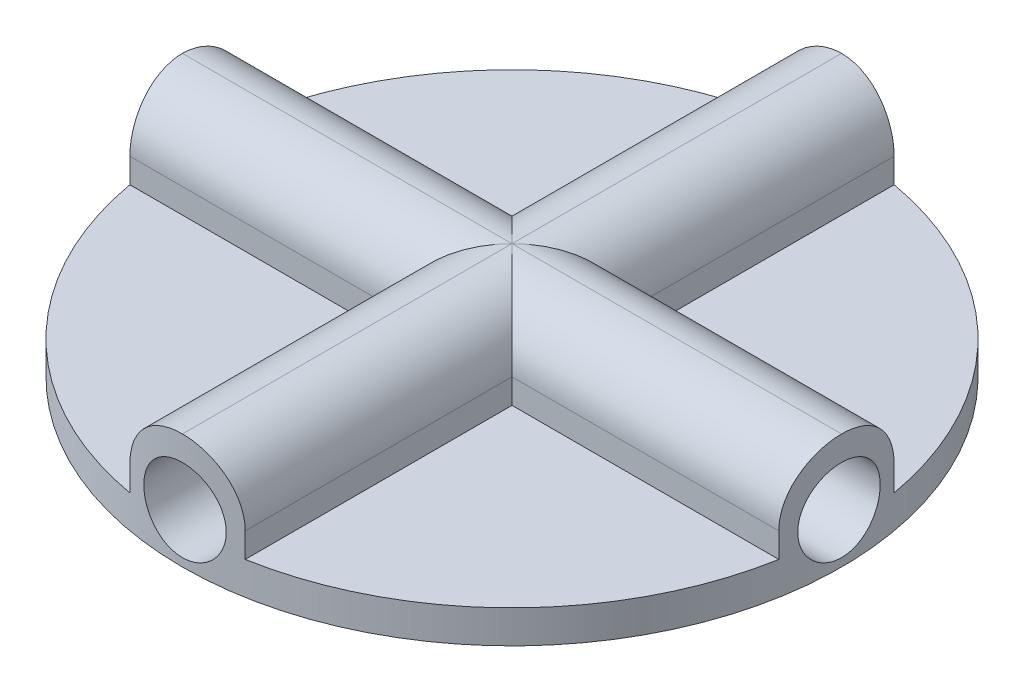
SolidWorks part; units mm, degrees
ref_plane "Front Plane" through (0, 0, 0) normal (0, 0, 1) x (1, 0, 0)
ref_plane "Top Plane" through (0, 0, 0) normal (0, 1, 0) x (1, 0, 0)
ref_plane "Right Plane" through (0, 0, 0) normal (1, 0, 0) x (0, 0, -1)
sketch "Sketch1" plane through (0, 0, 0) normal (0, 1, 0) x (1, 0, 0)
  circle A0 centre (0, 0) radius 20
  circle A1 centre (0, 0) radius 3
  dimension "D1" = 40
  dimension "D2" = 6
extrude "Boss-Extrude1" add sketch "Sketch1" along normal blind 7 contours A0
sketch "Sketch8" plane through (0, 0, 0) normal (0, 0, 1) x (1, 0, 0)
  line L0 (-20, 0) -> (20, 0) construction
  circle A0 centre (0, 3) radius 2.5
  point P2 (0, 3.3742)
  dimension "D1" = 5
  dimension "3" = 3
extrude "Cut-Extrude4" cut sketch "Sketch8" against normal up to surface (19.8431 mm away) up to face at (0, 7, 20)
pattern_circular "CirPattern9" count 4 over 360 about axis through (0, 7, 0) along (0, -1, 0) of "Cut-Extrude4" reverse direction yes
sketch "Sketch9" plane through (0, 7, 0) normal (0, 1, 0) x (1, 0, 0)
  line L0 (-3.5, -3.5) -> (-3.5, -19.6914)
  line L1 (-3.5, -19.6914) -> (-22.3802, -19.6914)
  line L2 (-22.3802, -19.6914) -> (-22.3802, -3.5)
  line L3 (-22.3802, -3.5) -> (-3.5, -3.5)
  circle A0 centre (0, 0) radius 20 construction
  point P4 (0, 0)
  dimension "D1" = 1
  dimension "D2" = 1
extrude "Cut-Extrude5" cut sketch "Sketch9" against normal blind 5
pattern_circular "CirPattern10" count 4 over 360 about axis through (0, 0, 0) along (0, 1, 0) of "Cut-Extrude5"
fillet "Fillet1" radius 3.5 8 edges at (-3.5, 7, -11.5957) (3.5, 7, -11.5957) (11.5957, 7, -3.5) (11.5957, 7, 3.5) (3.5, 7, 11.5957) (-3.5, 7, 11.5957) (-11.5957, 7, 3.5) (-11.5957, 7, -3.5)
